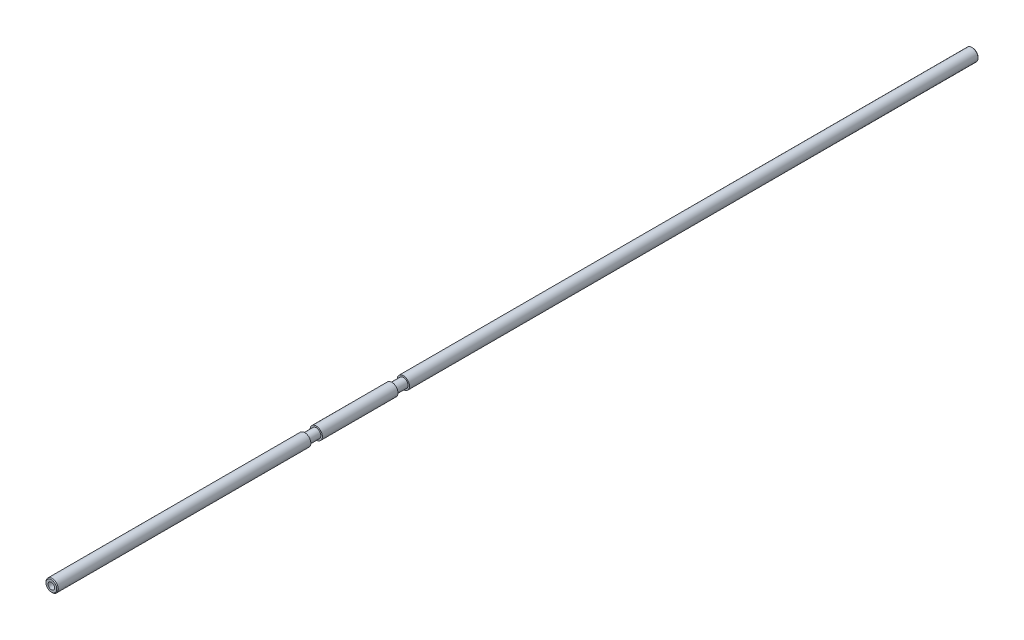
SolidWorks part; units mm, degrees
ref_plane "Front Plane" through (0, 0, 0) normal (0, 0, 1) x (1, 0, 0)
ref_plane "Top Plane" through (0, 0, 0) normal (0, 1, 0) x (1, 0, 0)
ref_plane "Right Plane" through (0, 0, 0) normal (1, 0, 0) x (0, 0, -1)
sketch "Sketch1" plane through (0, 0, 0) normal (0, 0, 1) x (1, 0, 0)
  circle A0 centre (-45, 0) radius 8
  dimension "D1" = 16
  dimension "D2" = 45
extrude "Boss-Extrude1" add sketch "Sketch1" along normal blind 1200 from offset 10
chamfer "Chamfer1" distance 1 angle 45 2 edges at (-37, 0, 1210) (-37, 0, 10)
sketch "Sketch2" plane through (0, 0, 1210) normal (0, 0, 1) x (1, 0, 0)
  circle A0 centre (-45, 0) radius 4.25
  dimension "D1" = 8.5
extrude "Cut-Extrude1" cut sketch "Sketch2" against normal blind 50
sketch "Sketch3" plane through (0, 0, 10) normal (0, 0, -1) x (-1, 0, 0)
  circle A0 centre (45, 0) radius 4.25
  dimension "D1" = 8.5
extrude "Cut-Extrude2" cut sketch "Sketch3" against normal blind 50
sketch "Sketch4" plane through (0, 0, 1210) normal (0, 0, 1) x (1, 0, 0)
  circle A0 centre (-45, 0) radius 8 construction
  circle A1 centre (-45, 0) radius 8
  circle A2 centre (-45, 0) radius 6
  dimension "D1" = 12
extrude "Cut-Extrude3" cut sketch "Sketch4" against normal blind 15 from offset 443.5 offset against normal yes
extrude "Cut-Extrude4" cut sketch "Sketch4<2>" against normal blind 15 from offset 330 offset against normal yes
sketch "Sketch4<2>" plane through (0, 0, 1210) normal (0, 0, 1) x (1, 0, 0) same geometry as "Sketch4"
